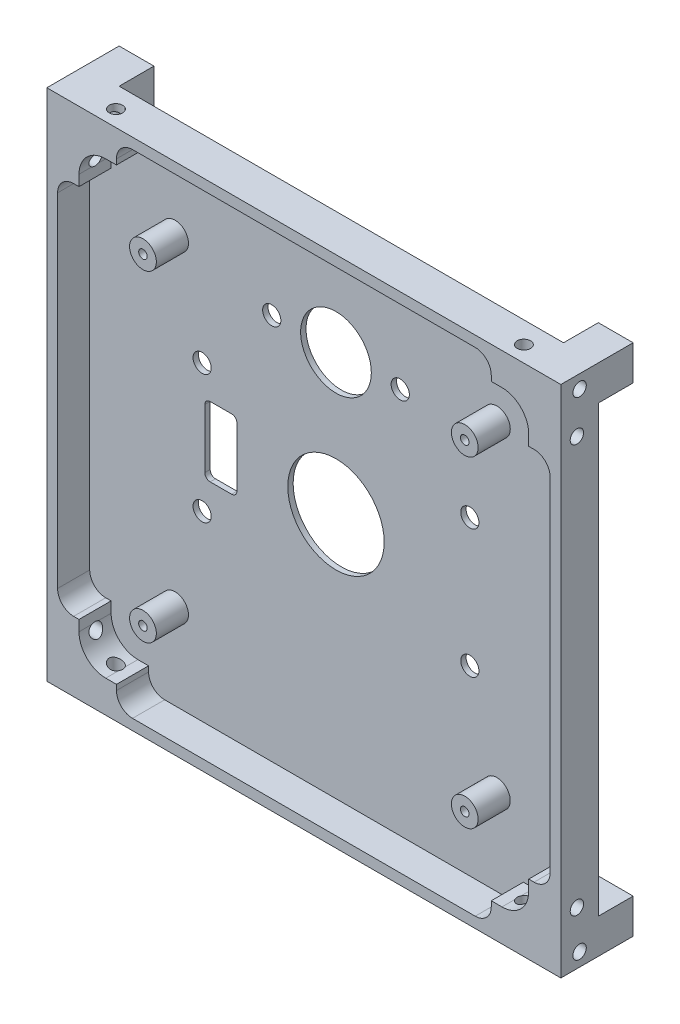
SolidWorks part; units mm, degrees
material "7075-T6 (SN)"
ref_plane "Front Plane" through (0, 0, 0) normal (0, 0, 1) x (1, 0, 0)
ref_plane "Top Plane" through (0, 0, 0) normal (0, 1, 0) x (1, 0, 0)
ref_plane "Right Plane" through (0, 0, 0) normal (1, 0, 0) x (0, 0, -1)
sketch "Sketch1" plane through (0, 0, 0) normal (0, 0, 1) x (1, 0, 0)
  line L1 (48, -48) -> (-48, -48)
  line L2 (48, -48) -> (48, 48)
  line L3 (48, 48) -> (-48, 48)
  line L4 (-48, -48) -> (-48, 48)
  line L5 (48, -48) -> (-48, 48) construction
  line L6 (48, 48) -> (-48, -48) construction
  point P0 (0, 0)
  dimension "D1" = 96
  dimension "D2" = 96
extrude "Boss-Extrude1" add sketch "Sketch1" along normal blind 2
sketch "Sketch2" plane through (0, 0, 2) normal (0, 0, 1) x (1, 0, 0)
  line L0 (48, 48) -> (-48, 48) construction
  line L1 (37, -42) -> (-37, -42)
  line L2 (42, -37) -> (42, 37)
  line L3 (37, 42) -> (-37, 42)
  line L4 (-42, -37) -> (-42, 37)
  line L5 (42, -42) -> (-42, 42) construction
  line L6 (42, 42) -> (-42, -42) construction
  line L7 (48, -48) -> (48, 48) construction
  line L12 (-48, 48) -> (-48, -48)
  line L13 (-48, -48) -> (48, -48)
  line L14 (48, -48) -> (48, 48)
  line L15 (48, 48) -> (-48, 48)
  line L16 (-48, 48) -> (-48, -48)
  line L17 (-48, -48) -> (48, -48)
  line L18 (48, -48) -> (48, 48)
  line L19 (48, 48) -> (-48, 48)
  arc A0 (-37, -42) -> (-42, -37) centre (-37, -37) cw
  arc A1 (37, -42) -> (42, -37) centre (37, -37) ccw
  arc A2 (42, 37) -> (37, 42) centre (37, 37) ccw
  arc A3 (-37, 42) -> (-42, 37) centre (-37, 37) ccw
  point P0 (0, 0)
  dimension "D4" = 5
  dimension "D1" = 6
  dimension "D2" = 6
extrude "Boss-Extrude2" add sketch "Sketch2" along normal blind 5
sketch "Sketch4" plane through (0, 0, 7) normal (0, 0, 1) x (1, 0, 0)
  line L0 (-41.5, 41.5) -> (41.5, -41.5) construction
  line L1 (-41.5, 41.5) -> (41.5, 41.5)
  line L2 (-41.5, 41.5) -> (-41.5, -41.5)
  line L3 (-41.5, -41.5) -> (41.5, -41.5)
  line L4 (41.5, 41.5) -> (41.5, -41.5)
  point P4 (0, 0)
  dimension "D1" = 83
  dimension "D2" = 83
sketch "Sketch3" plane through (0, 0, 0) normal (0, 0, -1) x (-1, 0, 0)
  line L1 (-48, 48) -> (-41.5, 48)
  line L2 (-48, 48) -> (-48, 41.5)
  line L3 (-48, 41.5) -> (-41.5, 41.5)
  line L4 (-41.5, 48) -> (-41.5, 41.5)
  line L5 (48, 48) -> (41.5, 48)
  line L6 (48, 48) -> (48, 41.5)
  line L7 (48, 41.5) -> (41.5, 41.5)
  line L8 (41.5, 48) -> (41.5, 41.5)
  line L9 (-48, -48) -> (-41.5, -48)
  line L10 (-48, -48) -> (-48, -41.5)
  line L11 (-48, -41.5) -> (-41.5, -41.5)
  line L12 (-41.5, -48) -> (-41.5, -41.5)
  line L13 (48, -48) -> (41.5, -48)
  line L14 (48, -48) -> (48, -41.5)
  line L15 (48, -41.5) -> (41.5, -41.5)
  line L16 (41.5, -48) -> (41.5, -41.5)
  dimension "D1" = 6.5
  dimension "D2" = 6.5
  dimension "D3" = 6.5
  dimension "D4" = 6.5
extrude "Boss-Extrude3" add sketch "Sketch3" along normal blind 6.5
sketch "Sketch5" plane through (0, 0, 0) normal (0, 0, -1) x (-1, 0, 0)
  circle A0 centre (0, 0) radius 9
  dimension "D1" = 18
extrude "Cut-Extrude1" cut sketch "Sketch5" against normal blind 10
sketch "Sketch6" plane through (-48, 0, 0) normal (-1, 0, 0) x (0, 0, 1)
  line L0 (-6.5, -45.5) -> (7, -45.5) construction
  line L2 (7, 48) -> (7, -48) construction
  line L3 (-6.5, 45.5) -> (7, 45.5) construction
  line L5 (7, 48) -> (-6.5, 48) construction
  line L6 (7, -48) -> (-6.5, -48) construction
  point P6 (3.5, -45.5)
  point P11 (3.5, 45.5)
  dimension "D1" = 3.5
  dimension "D2" = 3.5
  dimension "D3" = 2.5
  dimension "D4" = 2.5
hole_wizard "M3 Tapped Hole1" positions "3DSketch1" profile "Sketch7" tap size "M3" standard "ISO"
sketch3d "3DSketch1"
  point P0 (-48, 45.5, 3.5)
  point P3 (-48, -45.5, 3.5)
sketch "Sketch7" plane through (-48, 45.5, 3.5) normal (0, 1, 0) x (0, 0, 1)
  line L0 (0, 0) -> (0, 10.2511)
  line L1 (0, 10.2511) -> (1.25, 9.5)
  line L2 (1.25, 9.5) -> (1.25, 0)
  line L5 (1.25, 0) -> (0, 0)
  line L10 (0, 10.2511) -> (-1.25, 9.5) construction
  line L11 (0, -6.35) -> (0, 107.95) construction
  dimension "Tap Drill Dia." = 2.5
  dimension "Tap Drill Depth" = 9.5
  dimension "Drill Angle" = 118
cosmetic thread "Hole Thread1" parameters "D1"=8, "D2"=3
cosmetic thread "Hole Thread2" parameters "D1"=8, "D2"=3
mirror "Mirror1" about plane through (0, 0, 0) normal (1, 0, 0) of "M3 Tapped Hole1"
sketch "Sketch8" plane through (48, 0, 0) normal (1, 0, 0) x (0, 0, -1)
  point P0 (-4, -38.0996)
  point P1 (-4, 38.1004)
hole_wizard "M3 Tapped Hole2" positions "3DSketch2" profile "Sketch10" tap size "M3" standard "ISO"
sketch3d "3DSketch2"
  point P0 (48, 38.1004, 4)
  point P3 (48, -38.0996, 4)
sketch "Sketch10" plane through (48, 38.1004, 4) normal (0, 1, 0) x (0, 0, -1)
  line L0 (0, 0) -> (0, 9.2511)
  line L1 (0, 9.2511) -> (1.25, 8.5)
  line L2 (1.25, 8.5) -> (1.25, 0)
  line L5 (1.25, 0) -> (0, 0)
  line L10 (0, 9.2511) -> (-1.25, 8.5) construction
  line L11 (0, -6.35) -> (0, 107.95) construction
  dimension "Tap Drill Dia." = 2.5
  dimension "Tap Drill Depth" = 8.5
  dimension "Drill Angle" = 118
cosmetic thread "Hole Thread3" parameters "D1"=6, "D2"=3
cosmetic thread "Hole Thread4" parameters "D1"=6, "D2"=3
ref_axis "Axis1" through (0, 0, 2) along (0, 0, -1)
pattern_circular "CirPattern1" count 4 every 90 about axis through (0, 0, 2) along (0, 0, -1) of "M3 Tapped Hole2"
sketch "Sketch11" plane through (0, 0, 7) normal (0, 0, 1) x (1, 0, 0)
  line L0 (-37, -42) -> (37, -42) construction
  line L1 (32, -46) -> (-32, -46)
  line L2 (35, -43) -> (35, -42)
  line L3 (35, -42) -> (-35, -42)
  line L4 (-35, -43) -> (-35, -42)
  line L5 (-48, -48) -> (48, -48) construction
  line L6 (48, -48) -> (48, 48) construction
  line L7 (-48, 48) -> (-48, -48) construction
  line L8 (48, 48) -> (-48, 48) construction
  line L9 (-42, -35) -> (-43, -35)
  line L10 (-42, -35) -> (-42, 35)
  line L11 (-42, 35) -> (-43, 35)
  line L12 (-37, -42) -> (37, -42)
  line L13 (42, -37) -> (42, 37)
  line L14 (37, 42) -> (-37, 42)
  line L15 (-42, 37) -> (-42, -37)
  line L16 (-37, -42) -> (37, -42)
  line L17 (42, -37) -> (42, 37)
  line L18 (37, 42) -> (-37, 42)
  line L19 (-42, 37) -> (-42, -37)
  line L20 (-46, -32) -> (-46, 32)
  arc A0 (-43, 35) -> (-46, 32) centre (-43, 32) ccw
  arc A1 (-43, -35) -> (-46, -32) centre (-43, -32) cw
  arc A2 (-32, -46) -> (-35, -43) centre (-32, -43) cw
  arc A3 (32, -46) -> (35, -43) centre (32, -43) ccw
  arc A4 (-42, -37) -> (-37, -42) centre (-37, -37) ccw
  arc A5 (37, -42) -> (42, -37) centre (37, -37) ccw
  arc A6 (42, 37) -> (37, 42) centre (37, 37) ccw
  arc A7 (-37, 42) -> (-42, 37) centre (-37, 37) ccw
  arc A8 (-42, -37) -> (-37, -42) centre (-37, -37) ccw
  arc A9 (37, -42) -> (42, -37) centre (37, -37) ccw
  arc A10 (42, 37) -> (37, 42) centre (37, 37) ccw
  arc A11 (-37, 42) -> (-42, 37) centre (-37, 37) ccw
  point P10 (-35, -42.5)
  line M21 (37, -42) -> (-37, -42)
  line M23 (-42, -37) -> (-42, 37)
  dimension "D1" = 2
  dimension "D8" = 3
  dimension "D2" = 13
  dimension "D3" = 13
  dimension "D5" = 13
  dimension "D6" = 13
  dimension "D7" = 2
extrude "Cut-Extrude2" cut sketch "Sketch11" against normal up to surface (5 mm away) contours A1 L9 L11 A0 L20 M23 | L1 A3 L2 L4 A2 M21 region at (0, -43.9814, 7) region at (-43.9814, 0, 7) up to face at (9, 0, 2)
pattern_circular "CirPattern2" count 2 every 180 about axis through (0, 0, 2) along (0, 0, -1) of "Cut-Extrude2"
sketch "Sketch12" plane through (0, 0, 2) normal (0, 0, 1) x (1, 0, 0)
  line L20 (-37, -42) -> (-35, -42)
  line L21 (-35, -42) -> (-35, -43)
  line L22 (-32, -46) -> (32, -46)
  line L23 (35, -43) -> (35, -42)
  line L24 (35, -42) -> (37, -42)
  line L25 (42, -37) -> (42, -35)
  line L26 (42, -35) -> (43, -35)
  line L27 (46, -32) -> (46, 32)
  line L28 (43, 35) -> (42, 35)
  line L29 (42, 35) -> (42, 37)
  line L30 (37, 42) -> (35, 42)
  line L31 (35, 42) -> (35, 43)
  line L32 (32, 46) -> (-32, 46)
  line L33 (-35, 43) -> (-35, 42)
  line L34 (-35, 42) -> (-37, 42)
  line L35 (-42, 37) -> (-42, 35)
  line L36 (-42, 35) -> (-43, 35)
  line L37 (-46, 32) -> (-46, -32)
  line L38 (-43, -35) -> (-42, -35)
  line L39 (-42, -35) -> (-42, -37)
  line L40 (-37, -42) -> (-35, -42)
  line L41 (-35, -42) -> (-35, -43)
  line L42 (-32, -46) -> (32, -46)
  line L43 (35, -43) -> (35, -42)
  line L44 (35, -42) -> (37, -42)
  line L45 (42, -37) -> (42, -35)
  line L46 (42, -35) -> (43, -35)
  line L47 (46, -32) -> (46, 32)
  line L48 (43, 35) -> (42, 35)
  line L49 (42, 35) -> (42, 37)
  line L50 (37, 42) -> (35, 42)
  line L51 (35, 42) -> (35, 43)
  line L52 (32, 46) -> (-32, 46)
  line L53 (-35, 43) -> (-35, 42)
  line L54 (-35, 42) -> (-37, 42)
  line L55 (-42, 37) -> (-42, 35)
  line L56 (-42, 35) -> (-43, 35)
  line L57 (-46, 32) -> (-46, -32)
  line L58 (-43, -35) -> (-42, -35)
  line L59 (-42, -35) -> (-42, -37)
  arc A12 (-42, -37) -> (-37, -42) centre (-37, -37) ccw
  arc A13 (-35, -43) -> (-32, -46) centre (-32, -43) ccw
  arc A14 (32, -46) -> (35, -43) centre (32, -43) ccw
  arc A15 (37, -42) -> (42, -37) centre (37, -37) ccw
  arc A16 (43, -35) -> (46, -32) centre (43, -32) ccw
  arc A17 (46, 32) -> (43, 35) centre (43, 32) ccw
  arc A18 (42, 37) -> (37, 42) centre (37, 37) ccw
  arc A19 (35, 43) -> (32, 46) centre (32, 43) ccw
  arc A20 (-32, 46) -> (-35, 43) centre (-32, 43) ccw
  arc A21 (-37, 42) -> (-42, 37) centre (-37, 37) ccw
  arc A22 (-43, 35) -> (-46, 32) centre (-43, 32) ccw
  arc A23 (-46, -32) -> (-43, -35) centre (-43, -32) ccw
  arc A24 (-42, -37) -> (-37, -42) centre (-37, -37) ccw
  arc A25 (-35, -43) -> (-32, -46) centre (-32, -43) ccw
  arc A26 (32, -46) -> (35, -43) centre (32, -43) ccw
  arc A27 (37, -42) -> (42, -37) centre (37, -37) ccw
  arc A28 (43, -35) -> (46, -32) centre (43, -32) ccw
  arc A29 (46, 32) -> (43, 35) centre (43, 32) ccw
  arc A30 (42, 37) -> (37, 42) centre (37, 37) ccw
  arc A31 (35, 43) -> (32, 46) centre (32, 43) ccw
  arc A32 (-32, 46) -> (-35, 43) centre (-32, 43) ccw
  arc A33 (-37, 42) -> (-42, 37) centre (-37, 37) ccw
  arc A34 (-43, 35) -> (-46, 32) centre (-43, 32) ccw
  arc A35 (-46, -32) -> (-43, -35) centre (-43, -32) ccw
  dimension "D1" = 0
extrude "Cut-Extrude3" cut sketch "Sketch12" against normal blind 1
sketch "Sketch13" plane through (0, 0, 7) normal (0, 0, 1) x (1, 0, 0)
  line L4 (48, 48) -> (-48, 48)
  line L5 (-48, 48) -> (-48, -48)
  line L6 (-48, -48) -> (48, -48)
  line L7 (48, -48) -> (48, 48)
  line L8 (48, 48) -> (-48, 48)
  line L9 (-48, 48) -> (-48, -48)
  line L10 (-48, -48) -> (48, -48)
  line L11 (48, -48) -> (48, 48)
  dimension "D1" = 0
extrude "Cut-Extrude4" [suppressed] cut sketch "Sketch13" against normal blind 1
sketch "Sketch14" plane through (0, 0, 0) normal (0, 0, -1) x (-1, 0, 0)
  circle A0 centre (0, 0) radius 20
  text T0 "MSSG       -      EYE-SAT" font "Impact" height 4
  dimension "D1" = 40
sketch "Sketch15" plane through (0, 0, 1) normal (0, 0, 1) x (1, 0, 0)
  line L0 (0, 0) -> (-35.5279, 35.5279) construction
  line L1 (0, 0) -> (-32.9127, -32.9127) construction
  circle A0 centre (0, 0) radius 42.5 construction
  circle A1 centre (-30.052, 30.052) radius 2.5
  point P2 (30.052, 30.052)
  point P6 (30.052, -30.052)
  point P9 (-30.052, -30.052)
  point P10 (-30.052, 30.052)
extrude "Boss-Extrude4" add sketch "Sketch15" along normal blind 6
pattern_circular "CirPattern3" count 4 over 360 about axis through (0, 0, 2) along (0, 0, -1) of "Boss-Extrude4" reverse direction yes
hole_wizard "Tap Drill for M2x0.4 Tap1" positions "3DSketch3" profile "Sketch16" hole size "M2x0.4" standard "ANSI Metric"
sketch3d "3DSketch3"
  line L3 (-30.052, 30.052, 7) -> (-30.052, 30.052, 1) construction
  point P0 (-30.052, 30.052, 7)
  point P17 (-30.052, 30.052, 7)
sketch "Sketch16" plane through (-30.052, 30.052, 7) normal (1, 0, 0) x (0, -1, 0)
  line L0 (0, 0) -> (0, 6.4797)
  line L1 (0, 6.4797) -> (0.8, 5.999)
  line L2 (0.8, 5.999) -> (0.8, 0)
  line L5 (0.8, 0) -> (0, 0)
  line L10 (0, 6.4797) -> (-0.8, 5.999) construction
  line L11 (0, -6.35) -> (0, 107.95) construction
  dimension "Hole Dia." = 1.6
  dimension "Hole Depth" = 5.999
  dimension "Drill Angle" = 118
pattern_circular "CirPattern4" count 4 over 360 about axis through (0, 0, 2) along (0, 0, -1) of "Tap Drill for M2x0.4 Tap1"
sketch "Sketch17" plane through (0, 0, 1) normal (0, 0, 1) x (1, 0, 0)
  line L1 (-18.5, -6.5) -> (-24.5, -6.5)
  line L2 (-18.5, -6.5) -> (-18.5, 6.5)
  line L3 (-18.5, 6.5) -> (-24.5, 6.5)
  line L4 (-24.5, -6.5) -> (-24.5, 6.5)
  line L5 (-18.5, -6.5) -> (-24.5, 6.5) construction
  line L6 (-18.5, 6.5) -> (-24.5, -6.5) construction
  point P0 (-21.5, 0)
  dimension "D1" = 13
  dimension "D2" = 6
  dimension "D3" = 21.5
extrude "Cut-Extrude5" cut sketch "Sketch17" against normal blind 10
hole_wizard "M3 Clearance Hole1" positions "3DSketch4" profile "Sketch18" hole size "M3" standard "ANSI Metric" end condition through all
sketch3d "3DSketch4"
  point P0 (-25, -12, 1)
sketch "Sketch18" plane through (-25, -12, 1) normal (1, 0, 0) x (0, -1, 0)
  line L0 (0, 0) -> (0, 7.5)
  line L1 (0, 7.5) -> (1.7, 7.5)
  line L2 (1.7, 7.5) -> (1.7, 0)
  line L5 (1.7, 0) -> (0, 0)
  line L11 (0, -6.35) -> (0, 107.95) construction
  dimension "Thru Hole Dia." = 3.4
  dimension "Thru Hole Depth" = 7.5
hole_wizard "M3 Clearance Hole2" positions "Sketch22" profile "Sketch23" hole size "M3" standard "ISO"
sketch "Sketch22" plane through (0, 0, 1) normal (0, 0, 1) x (1, 0, 0)
  point P0 (-12, 26.2)
  point P2 (12, 26.2)
  dimension "D1" = 12
  dimension "D2" = 26.2
  dimension "D3" = 26.2
  dimension "D4" = 12
sketch "Sketch23" plane through (-12, 26.2, 1) normal (1, 0, 0) x (0, -1, 0)
  line L0 (0, 0) -> (0, 14.5515)
  line L1 (0, 14.5515) -> (1.7, 13.53)
  line L2 (1.7, 13.53) -> (1.7, 0)
  line L5 (1.7, 0) -> (0, 0)
  line L10 (0, 14.5515) -> (-1.7, 13.53) construction
  line L11 (0, -6.35) -> (0, 107.95) construction
  dimension "Hole Dia." = 3.4
  dimension "Hole Depth" = 13.53
  dimension "Drill Angle" = 118
sketch "Sketch24" plane through (0, 0, 1) normal (0, 0, 1) x (1, 0, 0)
  circle A0 centre (0, 26.2) radius 6.6
extrude "Cut-Extrude6" cut sketch "Sketch24" against normal blind 10
mirror "Mirror2" about plane through (0, 0, 0) normal (0, 1, 0) of "M3 Clearance Hole1"
mirror "Mirror3" about plane through (0, 0, 0) normal (1, 0, 0) of "M3 Clearance Hole1"
pattern_circular "CirPattern5" count 2 over 360 about axis through (0, 0, 2) along (0, 0, -1) of "M3 Clearance Hole1"
fillet "Fillet1" radius 1 4 edges at (-24.5, -6.5, 0.5) (-24.5, 6.5, 0.5) (-18.5, -6.5, 0.5) (-18.5, 6.5, 0.5)
equation "\"D2@Sketch1\"=\"D1@Sketch1\""
equation "\"thickness\" = 2"
equation "\"D1@Boss-Extrude1\"=\"thickness\""
equation "\"D2@Sketch2\"=\"D1@Sketch2\""
equation "\"D2@Sketch3\"=\"D1@Sketch3\""
equation "\"D3@Sketch3\"=\"D1@Sketch3\""
equation "\"D4@Sketch3\"=\"D1@Sketch3\""
equation "\"D2@Sketch4\"=\"D1@Sketch4\""
equation "\"D2@Sketch6\"=\"D1@Sketch6\""
equation "\"D4@Sketch6\"=\"D3@Sketch6\""
equation "\"D3@Sketch11\"=\"D2@Sketch11\""
equation "\"D5@Sketch11\"=\"D2@Sketch11\""
equation "\"D6@Sketch11\"=\"D2@Sketch11\""
equation "\"D7@Sketch11\"=\"D1@Sketch11\""
